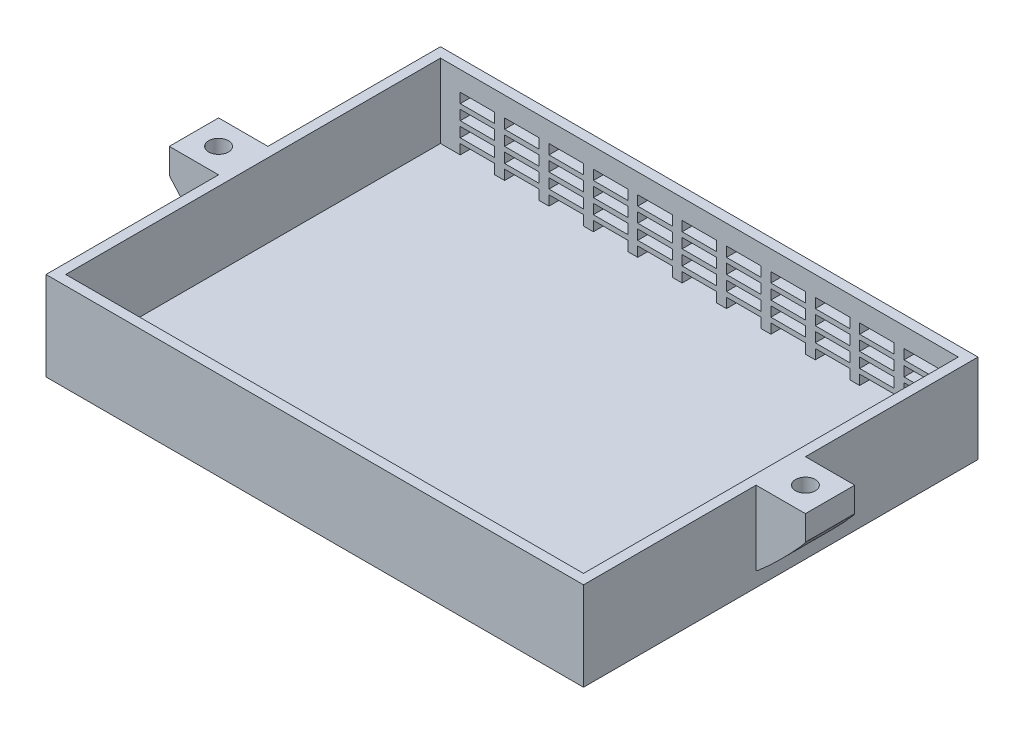
SolidWorks part; units mm, degrees
ref_plane "Front Plane" through (0, 0, 0) normal (0, 0, 1) x (1, 0, 0)
ref_plane "Top Plane" through (0, 0, 0) normal (0, 1, 0) x (1, 0, 0)
ref_plane "Right Plane" through (0, 0, 0) normal (1, 0, 0) x (0, 0, -1)
sketch "Sketch1" plane through (0, 0, 0) normal (0, 1, 0) x (1, 0, 0)
  line L1 (0, 0) -> (87.2, 0)
  line L2 (0, 0) -> (0, -64)
  line L3 (0, -64) -> (87.2, -64)
  line L4 (87.2, 0) -> (87.2, -64)
  dimension "D1" = 64
  dimension "D2" = 87.2
extrude "Boss-Extrude1" add sketch "Sketch1" along normal blind 2.4
sketch "Sketch2" plane through (0, 2.4, 0) normal (0, 1, 0) x (1, 0, 0)
  line L0 (85.6, -62.4) -> (85.6, -1.6)
  line L1 (87.2, -64) -> (0, -64)
  line L2 (87.2, -64) -> (87.2, 0)
  line L3 (87.2, 0) -> (0, 0)
  line L4 (0, -64) -> (0, 0)
  line L5 (85.6, -1.6) -> (1.6, -1.6)
  line L6 (1.6, -62.4) -> (1.6, -1.6)
  line L7 (85.6, -62.4) -> (1.6, -62.4)
  dimension "D1" = 1.6
extrude "Boss-Extrude2" add sketch "Sketch2" along normal blind 12
sketch "Sketch4" plane through (0, 0, 0) normal (0, 0, -1) x (-1, 0, 0)
  line L0 (-87.2, 0) -> (0, 0) construction
  line L1 (-4.8, 4) -> (-10.4, 4)
  line L2 (-4.8, 4) -> (-4.8, 2.4)
  line L3 (-4.8, 2.4) -> (-10.4, 2.4)
  line L4 (-10.4, 4) -> (-10.4, 2.4)
  line L5 (0, 14.4) -> (0, 0) construction
  line L6 (-12, 2.4) -> (-17.6, 2.4)
  line L7 (-17.6, 4) -> (-17.6, 2.4)
  line L8 (-12, 4) -> (-17.6, 4)
  line L9 (-12, 4) -> (-12, 2.4)
  line L10 (-19.2, 2.4) -> (-24.8, 2.4)
  line L11 (-24.8, 4) -> (-24.8, 2.4)
  line L12 (-19.2, 4) -> (-24.8, 4)
  line L13 (-19.2, 4) -> (-19.2, 2.4)
  line L14 (-26.4, 2.4) -> (-32, 2.4)
  line L15 (-32, 4) -> (-32, 2.4)
  line L16 (-26.4, 4) -> (-32, 4)
  line L17 (-26.4, 4) -> (-26.4, 2.4)
  line L18 (-33.6, 2.4) -> (-39.2, 2.4)
  line L19 (-39.2, 4) -> (-39.2, 2.4)
  line L20 (-33.6, 4) -> (-39.2, 4)
  line L21 (-33.6, 4) -> (-33.6, 2.4)
  line L22 (-40.8, 2.4) -> (-46.4, 2.4)
  line L23 (-46.4, 4) -> (-46.4, 2.4)
  line L24 (-40.8, 4) -> (-46.4, 4)
  line L25 (-40.8, 4) -> (-40.8, 2.4)
  line L26 (-48, 2.4) -> (-53.6, 2.4)
  line L27 (-53.6, 4) -> (-53.6, 2.4)
  line L28 (-48, 4) -> (-53.6, 4)
  line L29 (-48, 4) -> (-48, 2.4)
  line L30 (-55.2, 2.4) -> (-60.8, 2.4)
  line L31 (-60.8, 4) -> (-60.8, 2.4)
  line L32 (-55.2, 4) -> (-60.8, 4)
  line L33 (-55.2, 4) -> (-55.2, 2.4)
  line L34 (-12, 4.8) -> (-17.6, 4.8)
  line L35 (-17.6, 6.4) -> (-17.6, 4.8)
  line L36 (-12, 6.4) -> (-17.6, 6.4)
  line L37 (-12, 6.4) -> (-12, 4.8)
  line L38 (-19.2, 4.8) -> (-24.8, 4.8)
  line L39 (-24.8, 6.4) -> (-24.8, 4.8)
  line L40 (-19.2, 6.4) -> (-24.8, 6.4)
  line L41 (-19.2, 6.4) -> (-19.2, 4.8)
  line L42 (-26.4, 4.8) -> (-32, 4.8)
  line L43 (-32, 6.4) -> (-32, 4.8)
  line L44 (-26.4, 6.4) -> (-32, 6.4)
  line L45 (-26.4, 6.4) -> (-26.4, 4.8)
  line L46 (-33.6, 4.8) -> (-39.2, 4.8)
  line L47 (-39.2, 6.4) -> (-39.2, 4.8)
  line L48 (-33.6, 6.4) -> (-39.2, 6.4)
  line L49 (-33.6, 6.4) -> (-33.6, 4.8)
  line L50 (-40.8, 4.8) -> (-46.4, 4.8)
  line L51 (-46.4, 6.4) -> (-46.4, 4.8)
  line L52 (-40.8, 6.4) -> (-46.4, 6.4)
  line L53 (-40.8, 6.4) -> (-40.8, 4.8)
  line L54 (-48, 4.8) -> (-53.6, 4.8)
  line L55 (-53.6, 6.4) -> (-53.6, 4.8)
  line L56 (-48, 6.4) -> (-53.6, 6.4)
  line L57 (-48, 6.4) -> (-48, 4.8)
  line L58 (-55.2, 4.8) -> (-60.8, 4.8)
  line L59 (-60.8, 6.4) -> (-60.8, 4.8)
  line L60 (-55.2, 6.4) -> (-60.8, 6.4)
  line L61 (-55.2, 6.4) -> (-55.2, 4.8)
  line L62 (-12, 7.2) -> (-17.6, 7.2)
  line L63 (-17.6, 8.8) -> (-17.6, 7.2)
  line L64 (-12, 8.8) -> (-17.6, 8.8)
  line L65 (-12, 8.8) -> (-12, 7.2)
  line L66 (-19.2, 7.2) -> (-24.8, 7.2)
  line L67 (-24.8, 8.8) -> (-24.8, 7.2)
  line L68 (-19.2, 8.8) -> (-24.8, 8.8)
  line L69 (-19.2, 8.8) -> (-19.2, 7.2)
  line L70 (-26.4, 7.2) -> (-32, 7.2)
  line L71 (-32, 8.8) -> (-32, 7.2)
  line L72 (-26.4, 8.8) -> (-32, 8.8)
  line L73 (-26.4, 8.8) -> (-26.4, 7.2)
  line L74 (-33.6, 7.2) -> (-39.2, 7.2)
  line L75 (-39.2, 8.8) -> (-39.2, 7.2)
  line L76 (-33.6, 8.8) -> (-39.2, 8.8)
  line L77 (-33.6, 8.8) -> (-33.6, 7.2)
  line L78 (-40.8, 7.2) -> (-46.4, 7.2)
  line L79 (-46.4, 8.8) -> (-46.4, 7.2)
  line L80 (-40.8, 8.8) -> (-46.4, 8.8)
  line L81 (-40.8, 8.8) -> (-40.8, 7.2)
  line L82 (-48, 7.2) -> (-53.6, 7.2)
  line L83 (-53.6, 8.8) -> (-53.6, 7.2)
  line L84 (-48, 8.8) -> (-53.6, 8.8)
  line L85 (-48, 8.8) -> (-48, 7.2)
  line L86 (-55.2, 7.2) -> (-60.8, 7.2)
  line L87 (-60.8, 8.8) -> (-60.8, 7.2)
  line L88 (-55.2, 8.8) -> (-60.8, 8.8)
  line L89 (-55.2, 8.8) -> (-55.2, 7.2)
  line L90 (-4.8, 4.8) -> (-10.4, 4.8)
  line L91 (-10.4, 6.4) -> (-10.4, 4.8)
  line L92 (-4.8, 6.4) -> (-10.4, 6.4)
  line L93 (-4.8, 6.4) -> (-4.8, 4.8)
  line L94 (-4.8, 7.2) -> (-10.4, 7.2)
  line L95 (-10.4, 8.8) -> (-10.4, 7.2)
  line L96 (-4.8, 8.8) -> (-10.4, 8.8)
  line L97 (-4.8, 8.8) -> (-4.8, 7.2)
  line L98 (-4.8, 9.6) -> (-10.4, 9.6)
  line L99 (-10.4, 11.2) -> (-10.4, 9.6)
  line L100 (-4.8, 11.2) -> (-10.4, 11.2)
  line L101 (-4.8, 11.2) -> (-4.8, 9.6)
  line L102 (-12, 9.6) -> (-17.6, 9.6)
  line L103 (-17.6, 11.2) -> (-17.6, 9.6)
  line L104 (-12, 11.2) -> (-17.6, 11.2)
  line L105 (-12, 11.2) -> (-12, 9.6)
  line L106 (-19.2, 9.6) -> (-24.8, 9.6)
  line L107 (-24.8, 11.2) -> (-24.8, 9.6)
  line L108 (-19.2, 11.2) -> (-24.8, 11.2)
  line L109 (-19.2, 11.2) -> (-19.2, 9.6)
  line L110 (-26.4, 9.6) -> (-32, 9.6)
  line L111 (-32, 11.2) -> (-32, 9.6)
  line L112 (-26.4, 11.2) -> (-32, 11.2)
  line L113 (-26.4, 11.2) -> (-26.4, 9.6)
  line L114 (-33.6, 9.6) -> (-39.2, 9.6)
  line L115 (-39.2, 11.2) -> (-39.2, 9.6)
  line L116 (-33.6, 11.2) -> (-39.2, 11.2)
  line L117 (-33.6, 11.2) -> (-33.6, 9.6)
  line L118 (-40.8, 9.6) -> (-46.4, 9.6)
  line L119 (-46.4, 11.2) -> (-46.4, 9.6)
  line L120 (-40.8, 11.2) -> (-46.4, 11.2)
  line L121 (-40.8, 11.2) -> (-40.8, 9.6)
  line L122 (-48, 9.6) -> (-53.6, 9.6)
  line L123 (-53.6, 11.2) -> (-53.6, 9.6)
  line L124 (-48, 11.2) -> (-53.6, 11.2)
  line L125 (-48, 11.2) -> (-48, 9.6)
  line L126 (-55.2, 9.6) -> (-60.8, 9.6)
  line L127 (-60.8, 11.2) -> (-60.8, 9.6)
  line L128 (-55.2, 11.2) -> (-60.8, 11.2)
  line L129 (-55.2, 11.2) -> (-55.2, 9.6)
  line L130 (-62.4, 2.4) -> (-68, 2.4)
  line L131 (-68, 4) -> (-68, 2.4)
  line L132 (-62.4, 4) -> (-68, 4)
  line L133 (-62.4, 4) -> (-62.4, 2.4)
  line L134 (-69.6, 2.4) -> (-75.2, 2.4)
  line L135 (-75.2, 4) -> (-75.2, 2.4)
  line L136 (-69.6, 4) -> (-75.2, 4)
  line L137 (-69.6, 4) -> (-69.6, 2.4)
  line L138 (-76.8, 2.4) -> (-82.4, 2.4)
  line L139 (-82.4, 4) -> (-82.4, 2.4)
  line L140 (-76.8, 4) -> (-82.4, 4)
  line L141 (-76.8, 4) -> (-76.8, 2.4)
  line L146 (-62.4, 4.8) -> (-68, 4.8)
  line L147 (-68, 6.4) -> (-68, 4.8)
  line L148 (-62.4, 6.4) -> (-68, 6.4)
  line L149 (-62.4, 6.4) -> (-62.4, 4.8)
  line L150 (-69.6, 4.8) -> (-75.2, 4.8)
  line L151 (-75.2, 6.4) -> (-75.2, 4.8)
  line L152 (-69.6, 6.4) -> (-75.2, 6.4)
  line L153 (-69.6, 6.4) -> (-69.6, 4.8)
  line L154 (-76.8, 4.8) -> (-82.4, 4.8)
  line L155 (-82.4, 6.4) -> (-82.4, 4.8)
  line L156 (-76.8, 6.4) -> (-82.4, 6.4)
  line L157 (-76.8, 6.4) -> (-76.8, 4.8)
  line L162 (-62.4, 7.2) -> (-68, 7.2)
  line L163 (-68, 8.8) -> (-68, 7.2)
  line L164 (-62.4, 8.8) -> (-68, 8.8)
  line L165 (-62.4, 8.8) -> (-62.4, 7.2)
  line L166 (-69.6, 7.2) -> (-75.2, 7.2)
  line L167 (-75.2, 8.8) -> (-75.2, 7.2)
  line L168 (-69.6, 8.8) -> (-75.2, 8.8)
  line L169 (-69.6, 8.8) -> (-69.6, 7.2)
  line L170 (-76.8, 7.2) -> (-82.4, 7.2)
  line L171 (-82.4, 8.8) -> (-82.4, 7.2)
  line L172 (-76.8, 8.8) -> (-82.4, 8.8)
  line L173 (-76.8, 8.8) -> (-76.8, 7.2)
  line L178 (-62.4, 9.6) -> (-68, 9.6)
  line L179 (-68, 11.2) -> (-68, 9.6)
  line L180 (-62.4, 11.2) -> (-68, 11.2)
  line L181 (-62.4, 11.2) -> (-62.4, 9.6)
  line L182 (-69.6, 9.6) -> (-75.2, 9.6)
  line L183 (-75.2, 11.2) -> (-75.2, 9.6)
  line L184 (-69.6, 11.2) -> (-75.2, 11.2)
  line L185 (-69.6, 11.2) -> (-69.6, 9.6)
  line L186 (-76.8, 9.6) -> (-82.4, 9.6)
  line L187 (-82.4, 11.2) -> (-82.4, 9.6)
  line L188 (-76.8, 11.2) -> (-82.4, 11.2)
  line L189 (-76.8, 11.2) -> (-76.8, 9.6)
  dimension "D1" = 5.6
  dimension "D2" = 1.6
  dimension "D3" = 2.4
  dimension "D4" = 4.8
  dimension "D5" = 11
  dimension "D6" = 4
extrude "Cut-Extrude1" cut sketch "Sketch4" against normal blind 12
sketch "Sketch7" plane through (0, 14.4, 0) normal (0, 1, 0) x (1, 0, 0)
  line L0 (87.2, -64) -> (87.2, 0) construction
  line L1 (87.2, -36) -> (95.2, -36)
  line L2 (87.2, -36) -> (87.2, -28)
  line L3 (87.2, -28) -> (95.2, -28)
  line L4 (95.2, -36) -> (95.2, -28)
  line L5 (43.6, -64) -> (43.6, -51.727) construction
  line L6 (0, -64) -> (87.2, -64) construction
  line L7 (0, -36) -> (0, -28)
  line L8 (0, -36) -> (-8, -36)
  line L9 (0, -28) -> (-8, -28)
  line L10 (-8, -36) -> (-8, -28)
  circle A0 centre (91.2, -32) radius 1.6
  circle A1 centre (-4, -32) radius 1.6
  dimension "D4" = 3.2
  dimension "D5" = 4
  dimension "D1" = 8
  dimension "D2" = 8
  dimension "D3" = 28
  dimension "D6" = 4
extrude "Boss-Extrude4" add sketch "Sketch7" against normal blind 12
fillet "Fillet2" radius 8 2 edges at (-8, 2.4, 32) (95.2, 2.4, 32) conic rho 0.05
equation "\"D2@Sketch1\"=0.8*120-11.2+2.4"
